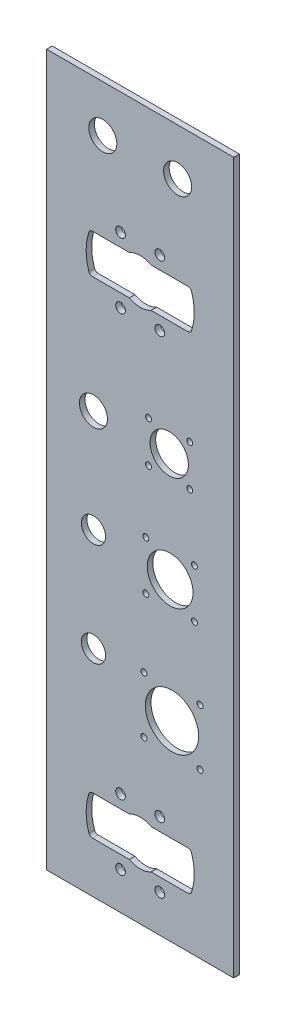
SolidWorks part; units mm, degrees
ref_plane "Front Plane" through (0, 0, 0) normal (0, 0, 1) x (1, 0, 0)
ref_plane "Top Plane" through (0, 0, 0) normal (0, 1, 0) x (1, 0, 0)
ref_plane "Right Plane" through (0, 0, 0) normal (1, 0, 0) x (0, 0, -1)
sketch "Sketch1" plane through (0, 0, 0) normal (0, 0, 1) x (1, 0, 0)
  line L0 (0, 260) -> (100, 260)
  line L1 (0, 0) -> (100, 0)
  line L2 (0, 0) -> (0, 380)
  line L3 (0, 380) -> (100, 380)
  line L4 (100, 0) -> (100, 380)
  line L5 (44.1905, 48) -> (24.4782, 48)
  line L6 (75.5218, 48) -> (55.8095, 48)
  line L7 (45, 255) -> (90, 255)
  line L8 (45, 190) -> (90, 190)
  line L9 (45, 190) -> (45, 145)
  line L10 (45, 145) -> (90, 145)
  line L11 (90, 190) -> (90, 145)
  line L12 (55.8095, 27) -> (75.5218, 27)
  line L13 (24.4782, 27) -> (44.1905, 27)
  line L14 (45, 255) -> (45, 210)
  line L15 (45, 210) -> (90, 210)
  line L16 (90, 255) -> (90, 210)
  line L17 (45, 125) -> (90, 125)
  line L22 (45, 125) -> (45, 80)
  line L23 (45, 80) -> (90, 80)
  line L24 (90, 125) -> (90, 80)
  line L25 (60.5, 55) -> (39.5, 55) construction
  line L26 (39.5, 55) -> (39.5, 20) construction
  line L27 (39.5, 20) -> (60.5, 20) construction
  line L29 (50, 55) -> (50, 20) construction
  line L30 (44.1905, 308) -> (24.4782, 308)
  line L31 (75.5218, 308) -> (55.8095, 308)
  line L32 (55.8095, 287) -> (75.5218, 287)
  line L33 (24.4782, 287) -> (44.1905, 287)
  line L34 (60.5, 315) -> (39.5, 315) construction
  line L35 (39.5, 315) -> (39.5, 280) construction
  line L36 (39.5, 280) -> (60.5, 280) construction
  line L37 (50, 315) -> (50, 280) construction
  line L39 (49, 120.5) -> (85, 120.5)
  line L40 (49, 120.5) -> (49, 84.5)
  line L41 (49, 84.5) -> (85, 84.5)
  line L42 (85, 120.5) -> (85, 84.5)
  line L44 (50, 183.5) -> (82, 183.5)
  line L45 (50, 183.5) -> (50, 151.5)
  line L46 (50, 151.5) -> (82, 151.5)
  line L47 (82, 183.5) -> (82, 151.5)
  line L49 (51, 240) -> (80, 240)
  line L50 (51, 240) -> (51, 211)
  line L51 (51, 211) -> (80, 211)
  line L52 (80, 240) -> (80, 211)
  circle A0 centre (50, 297.5) radius 32.5 construction
  circle A1 centre (50, 37.5) radius 32.5 construction
  circle A2 centre (25, 170) radius 6.5
  circle A4 centre (25, 115) radius 6.5
  circle A5 centre (25, 225) radius 7.5
  circle A6 centre (70, 355) radius 7.5
  circle A7 centre (30, 355) radius 7.5
  arc A8 (55.8095, 48) -> (44.1905, 48) centre (50, 37.5) ccw
  arc A9 (77.4193, 46.632) -> (75.5218, 48) centre (75.5218, 46) ccw
  arc A10 (77.4193, 28.368) -> (77.4193, 46.632) centre (50, 37.5) ccw
  arc A11 (75.5218, 27) -> (77.4193, 28.368) centre (75.5218, 29) ccw
  arc A12 (44.1905, 27) -> (55.8095, 27) centre (50, 37.5) ccw
  arc A13 (22.5807, 28.368) -> (24.4782, 27) centre (24.4782, 29) ccw
  arc A14 (22.5807, 46.632) -> (22.5807, 28.368) centre (50, 37.5) ccw
  arc A15 (24.4782, 48) -> (22.5807, 46.632) centre (24.4782, 46) ccw
  circle A16 centre (39.5, 20) radius 2.6
  circle A17 centre (60.5, 20) radius 2.6
  circle A18 centre (39.5, 55) radius 2.6
  circle A19 centre (60.5, 55) radius 2.6
  arc A20 (55.8095, 308) -> (44.1905, 308) centre (50, 297.5) ccw
  arc A21 (77.4193, 306.632) -> (75.5218, 308) centre (75.5218, 306) ccw
  arc A22 (77.4193, 288.368) -> (77.4193, 306.632) centre (50, 297.5) ccw
  arc A23 (75.5218, 287) -> (77.4193, 288.368) centre (75.5218, 289) ccw
  arc A24 (44.1905, 287) -> (55.8095, 287) centre (50, 297.5) ccw
  arc A25 (22.5807, 288.368) -> (24.4782, 287) centre (24.4782, 289) ccw
  arc A26 (22.5807, 306.632) -> (22.5807, 288.368) centre (50, 297.5) ccw
  arc A27 (24.4782, 308) -> (22.5807, 306.632) centre (24.4782, 306) ccw
  circle A28 centre (39.5, 280) radius 2.6
  circle A29 centre (60.5, 280) radius 2.6
  circle A30 centre (39.5, 315) radius 2.6
  circle A31 centre (60.5, 315) radius 2.6
  circle A32 centre (52, 117.5) radius 1.6
  circle A33 centre (82, 117.5) radius 1.6
  circle A34 centre (52, 87.5) radius 1.6
  circle A35 centre (82, 87.5) radius 1.6
  circle A36 centre (67, 102.5) radius 14.25
  circle A37 centre (66, 167.5) radius 12.25
  circle A38 centre (53, 180.5) radius 1.6
  circle A39 centre (79, 180.5) radius 1.6
  circle A40 centre (79, 154.5) radius 1.6
  circle A41 centre (53, 154.5) radius 1.6
  circle A42 centre (65.5, 225.5) radius 10.25
  circle A43 centre (54.5, 236.5) radius 1.6
  circle A44 centre (76.5, 236.5) radius 1.6
  circle A45 centre (54.5, 214.5) radius 1.6
  circle A46 centre (76.5, 214.5) radius 1.6
  point P0 (0, 0)
  dimension "D5" = 32.5
  dimension "D6" = 6.5
  dimension "D7" = 6.5
  dimension "D8" = 32.5
  dimension "D11" = 7.5
  dimension "D12" = 15
  dimension "D13" = 15
  dimension "D26" = 12
  dimension "D30" = 12
  dimension "D31" = 28.9
  dimension "D40" = 12
  dimension "D41" = 12
  dimension "D42" = 28.9
  dimension "D51" = 3.2
  dimension "D52" = 3.2
  dimension "D53" = 3.2
  dimension "D54" = 3.2
  dimension "D55" = 30
  dimension "D56" = 30
  dimension "D57" = 28.5
  dimension "D62" = 18
  dimension "D63" = 18
  dimension "D64" = 15
  dimension "D70" = 24.5
  dimension "D71" = 16
  dimension "D72" = 16
  dimension "D73" = 3.2
  dimension "D74" = 3.2
  dimension "D75" = 3.2
  dimension "D76" = 3.2
  dimension "D77" = 26
  dimension "D78" = 26
  dimension "D79" = 13
  dimension "D80" = 13
  dimension "D81" = 29
  dimension "D85" = 20.5
  dimension "D88" = 22
  dimension "D89" = 22
  dimension "D90" = 3.2
  dimension "D91" = 3.2
  dimension "D92" = 3.2
  dimension "D93" = 3.2
  dimension "D94" = 11
  dimension "D1" = 100
  dimension "D2" = 380
  dimension "D3" = 120
  dimension "D4" = 45
  dimension "D9" = 45
  dimension "D10" = 45
  dimension "D14" = 10
  dimension "D15" = 37.5
  dimension "D16" = 50
  dimension "D17" = 20
  dimension "D18" = 20
  dimension "D19" = 5
  dimension "D20" = 55
  dimension "D21" = 55
  dimension "D22" = 35
  dimension "D23" = 25
  dimension "D24" = 37.5
  dimension "D25" = 50
  dimension "D27" = 40
  dimension "D28" = 30
  dimension "D29" = 25
  dimension "D32" = 35
  dimension "D33" = 21
  dimension "D34" = 21
  dimension "D35" = 35
  dimension "D36" = 19.7123
  dimension "D37" = 19.7123
  dimension "D38" = 19.7123
  dimension "D39" = 19.7123
  dimension "D43" = 35
  dimension "D44" = 21
  dimension "D45" = 21
  dimension "D46" = 35
  dimension "D47" = 19.7123
  dimension "D48" = 19.7123
  dimension "D49" = 19.7123
  dimension "D50" = 19.7123
  dimension "D58" = 36
  dimension "D59" = 36
  dimension "D60" = 5
  dimension "D61" = 4.5
  dimension "D65" = 15
  dimension "D66" = 32
  dimension "D67" = 32
  dimension "D68" = 6.5
  dimension "D69" = 8
  dimension "D82" = 29
  dimension "D83" = 15
  dimension "D84" = 10
  dimension "D86" = 14.5
  dimension "D87" = 14.5
  dimension "D95" = 11
extrude "Boss-Extrude1" add sketch "Sketch1" against normal blind 3 contours L4 L3 L2 L1
extrude "Cut-Extrude1" cut sketch "Sketch1<3>" against normal up to surface (3 mm away) from surface contours A6 | A0 | A5 | L5 A15 A14 A13 L13 A12 L12 A11 A10 A9 L6 A8 | A16 | A17 | A19 | L30 A27 A26 A25 L33 A24 L32 A23 A22 A21 L31 A20 | A30 | A31 | A29 | A28 | A36 | A34 | A35 | A38 | A41 | A45 | A42 | A7 | A2 | A4 | A18 | A36 | A32 | A33 | A39 | A40 | A37 | A43 | A44 | A46 region at (50, 37.5, 0) region at (50, 297.5, 0) region at (25, 225, 0) region at (70, 355, 0) region at (39.5, 20, 0) region at (60.5, 20, 0) region at (60.5, 55, 0) region at (39.5, 280, 0) region at (60.5, 280, 0) region at (39.5, 315, 0) region at (60.5, 315, 0) region at (52, 87.5, 0) region at (82, 87.5, 0) region at (67, 102.5, 0) region at (53, 180.5, 0) region at (53, 154.5, 0) region at (65.5, 225.5, 0) region at (54.5, 214.5, 0) up to face at (50, 190, -3) starting at face at (50, 190, 0)
sketch "Sketch1<3>" plane through (0, 0, 0) normal (0, 0, 1) x (1, 0, 0) same geometry as "Sketch1"
